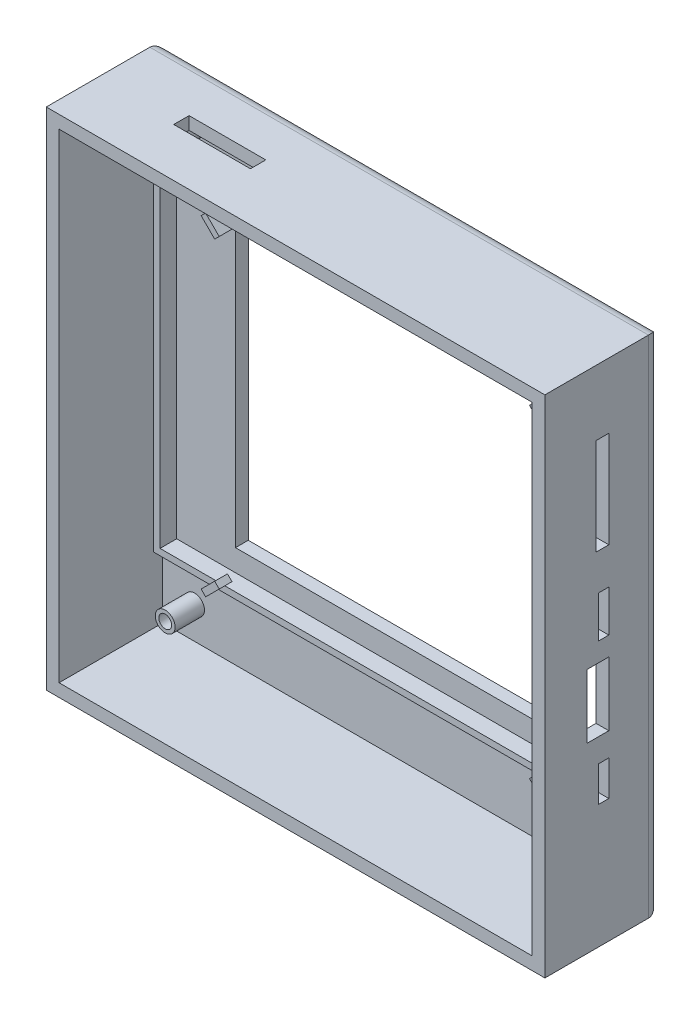
SolidWorks part; units mm, degrees
other "标注1"
sketch "草图10" plane through (-45.2426, 41.5897, 0) normal (-0.9994, 0.0059, 0.0328) x (0.0288, 0.6507, 0.7588)
ref_plane "前视基准面" through (0, 0, 0) normal (0, 0, 1) x (1, 0, 0)
ref_plane "上视基准面" through (0, 0, 0) normal (0, 1, 0) x (1, 0, 0)
ref_plane "右视基准面" through (0, 0, 0) normal (1, 0, 0) x (0, 0, -1)
sketch "外壳尺寸" plane through (0, 0, 0) normal (0, 0, 1) x (1, 0, 0)
  line L0 (-17.2361, -38.5079) -> (-14.2361, -38.5079)
  line L1 (38.764, -20.5078) -> (38.764, 15.4923)
  line L2 (-32.0459, 28.2943) -> (-38.764, 28.2943) construction
  line L3 (-32.0459, 13.1812) -> (-37.5195, 13.1812) construction
  line L4 (-33.9609, 7.4653) -> (-37.4846, 7.4653) construction
  line L5 (-33.9609, 0.9479) -> (-36.9615, 0.9479) construction
  line L6 (-34.7732, -15.6918) -> (-38.0077, -15.6918) construction
  line L7 (-34.7732, -21.1918) -> (-37.659, -21.1918) construction
  line L8 (-34.9146, -2.0109) -> (-36.6806, -2.0109) construction
  line L9 (-34.8191, -12.0127) -> (-36.3783, -12.0127) construction
  line L10 (16.4218, 37.9891) -> (16.4218, 33.2886) construction
  line L11 (28.422, 38.5079) -> (28.422, 33.6659) construction
  line L12 (-33.7426, -11.5127) -> (-35.165, -11.5127) construction
  line L13 (1.7639, 41.5897) -> (1.7639, -41.6804) construction
  line L14 (-35.165, -2.5109) -> (-33.7655, -2.5109) construction
  line L15 (45.0157, -1.0079) -> (-45.2426, -1.0079) construction
  line L16 (27.422, 35.861) -> (27.422, 36.7889) construction
  line L17 (17.4218, 35.861) -> (17.4218, 36.805) construction
  line L19 (-37.2361, -40.5079) -> (40.7639, -40.5079)
  line L20 (-37.2361, -40.5079) -> (-37.2361, 38.4921)
  line L21 (-37.2361, 38.4921) -> (40.7639, 38.4921)
  line L22 (40.7639, -40.5079) -> (40.7639, 38.4921)
  line L23 (-37.2361, -40.5079) -> (40.7639, 38.4921) construction
  line L24 (-37.2361, 38.4921) -> (40.7639, -40.5079) construction
  line L31 (-35.2362, -38.5079) -> (-17.2361, -38.5079)
  line L32 (-14.2361, -38.5079) -> (38.764, -38.5079)
  line L33 (38.764, -38.5079) -> (38.764, -20.5078)
  line L34 (38.764, 15.4923) -> (38.764, 36.4923)
  line L35 (38.764, 36.4923) -> (-35.2362, 36.4923)
  line L36 (-35.2362, 36.4923) -> (-35.2362, -38.5079)
  arc A0 (6.4148, 25.6401) -> (-2.8859, 25.6425) centre (1.7645, 25.6401) ccw construction
  arc A1 (-2.8859, 25.6377) -> (6.4148, 25.6401) centre (1.7645, 25.6401) ccw construction
  arc A2 (0.4641, 25.6357) -> (0.4641, 25.6425) centre (1.7641, 25.6391) ccw construction
  arc A3 (-2.2359, 25.6384) -> (-2.2359, 25.6425) centre (1.7643, 25.6405) ccw construction
  circle A4 centre (1.7639, 25.6423) radius 4.651 construction
  circle A5 centre (-30.1798, 31.4921) radius 1 construction
  circle A6 centre (33.764, 31.4923) radius 1 construction
  circle A7 centre (33.764, -33.5078) radius 1 construction
  circle A8 centre (-30.2361, -33.5078) radius 1 construction
  point P51 (1.7639, -1.0079)
  point P52 (1.7639, -1.0079)
  dimension "D9" = 2
  dimension "D10" = 2
  dimension "D11" = 2
  dimension "D12" = 2
  dimension "D21" = 4.6504
  dimension "D1" = 37.0001
  dimension "D2" = 37.5002
  dimension "D3" = 1
  dimension "D4" = 1
  dimension "D5" = 0.5
  dimension "D6" = 0.5
  dimension "D7" = 37.0001
  dimension "D8" = 37.5
  dimension "D13" = 5.0002
  dimension "D14" = 5.0564
  dimension "D15" = 5
  dimension "D16" = 5
  dimension "D17" = 5
  dimension "D18" = 5
  dimension "D19" = 5
  dimension "D20" = 5
  dimension "D22" = 10.8522
  dimension "D23" = 36.9995
  dimension "D24" = 78
  dimension "D25" = 79
sketch "上盖" plane through (0, 0, 0) normal (0, 0, 1) x (1, 0, 0)
  line L0 (-17.2361, -38.5079) -> (-14.2361, -38.5079)
  line L1 (38.764, -20.5078) -> (38.764, 15.4923)
  line L2 (-32.0459, 28.2943) -> (-38.764, 28.2943) construction
  line L3 (-32.0459, 13.1812) -> (-37.5195, 13.1812) construction
  line L4 (-33.9609, 7.4653) -> (-37.4846, 7.4653) construction
  line L5 (-33.9609, 0.9479) -> (-36.9615, 0.9479) construction
  line L6 (-34.7732, -15.6918) -> (-38.0077, -15.6918) construction
  line L7 (-34.7732, -21.1918) -> (-37.659, -21.1918) construction
  line L8 (-34.9146, -2.0109) -> (-36.6806, -2.0109) construction
  line L9 (-34.8191, -12.0127) -> (-36.3783, -12.0127) construction
  line L10 (16.4218, 37.9891) -> (16.4218, 33.2886) construction
  line L11 (28.422, 38.5079) -> (28.422, 33.6659) construction
  line L12 (-33.7426, -11.5127) -> (-35.165, -11.5127) construction
  line L13 (1.7639, 41.5897) -> (1.7639, -41.6804) construction
  line L14 (-35.165, -2.5109) -> (-33.7655, -2.5109) construction
  line L15 (45.0157, -1.0079) -> (-45.2426, -1.0079) construction
  line L16 (27.422, 35.861) -> (27.422, 36.7889) construction
  line L17 (17.4218, 35.861) -> (17.4218, 36.805) construction
  line L19 (-37.2361, -40.5079) -> (40.7639, -40.5079)
  line L20 (-37.2361, -40.5079) -> (-37.2361, 38.4921)
  line L21 (-37.2361, 38.4921) -> (40.7639, 38.4921)
  line L22 (40.7639, -40.5079) -> (40.7639, 38.4921)
  line L23 (-37.2361, -40.5079) -> (40.7639, 38.4921) construction
  line L24 (-37.2361, 38.4921) -> (40.7639, -40.5079) construction
  line L31 (-35.2362, -38.5079) -> (-17.2361, -38.5079)
  line L32 (-14.2361, -38.5079) -> (38.764, -38.5079)
  line L33 (38.764, -38.5079) -> (38.764, -20.5078)
  line L34 (38.764, 15.4923) -> (38.764, 36.4923)
  line L35 (38.764, 36.4923) -> (-35.2362, 36.4923)
  line L36 (-35.2362, 36.4923) -> (-35.2362, -38.5079)
  arc A0 (6.4148, 25.6401) -> (-2.8859, 25.6425) centre (1.7645, 25.6401) ccw construction
  arc A1 (-2.8859, 25.6377) -> (6.4148, 25.6401) centre (1.7645, 25.6401) ccw construction
  arc A2 (0.4641, 25.6357) -> (0.4641, 25.6425) centre (1.7641, 25.6391) ccw construction
  arc A3 (-2.2359, 25.6384) -> (-2.2359, 25.6425) centre (1.7643, 25.6405) ccw construction
  circle A4 centre (1.7639, 25.6423) radius 4.651 construction
  circle A5 centre (-30.1798, 31.4921) radius 1 construction
  circle A6 centre (33.764, 31.4923) radius 1 construction
  circle A7 centre (33.764, -33.5078) radius 1 construction
  circle A8 centre (-30.2361, -33.5078) radius 1 construction
  point P51 (1.7639, -1.0079)
  point P52 (1.7639, -1.0079)
  point P59 (16.4218, 36.4923)
  point P60 (28.422, 36.4923)
  dimension "D9" = 2
  dimension "D10" = 2
  dimension "D11" = 2
  dimension "D12" = 2
  dimension "D21" = 4.6504
  dimension "D1" = 37.0001
  dimension "D2" = 37.5002
  dimension "D3" = 1
  dimension "D4" = 1
  dimension "D5" = 0.5
  dimension "D6" = 0.5
  dimension "D7" = 37.0001
  dimension "D8" = 37.5
  dimension "D13" = 5.0002
  dimension "D14" = 5.0564
  dimension "D15" = 5
  dimension "D16" = 5
  dimension "D17" = 5
  dimension "D18" = 5
  dimension "D19" = 5
  dimension "D20" = 5
  dimension "D22" = 10.8522
  dimension "D23" = 36.9995
  dimension "D24" = 78
  dimension "D25" = 79
extrude "外壳" add sketch "上盖" against normal blind 18.2
sketch "上盖面板" plane through (0, 0, -18.2) normal (0, 0, -1) x (-1, 0, 0)
  line L0 (35.2362, 36.4923) -> (35.2362, -38.5079) construction
  line L1 (35.2362, 36.4923) -> (35.2362, -38.5079)
  line L2 (17.2361, -38.5079) -> (14.2361, -38.5079) construction
  line L3 (35.2362, -38.5079) -> (17.2361, -38.5079) construction
  line L4 (-40.7639, 38.4921) -> (-40.7639, -40.5079)
  line L5 (-40.7639, -40.5079) -> (37.2361, -40.5079)
  line L6 (37.2361, -40.5079) -> (37.2361, 38.4921)
  line L7 (37.2361, 38.4921) -> (-40.7639, 38.4921)
  line L8 (-40.7639, 38.4921) -> (-40.7639, -40.5079)
  line L9 (-40.7639, -40.5079) -> (37.2361, -40.5079)
  line L10 (37.2361, -40.5079) -> (37.2361, 38.4921)
  line L11 (37.2361, 38.4921) -> (-40.7639, 38.4921)
  line L12 (14.2361, -38.5079) -> (-38.764, -38.5079) construction
  line L13 (-38.764, -38.5079) -> (-38.764, -20.5078) construction
  line L14 (-38.764, -20.5078) -> (-38.764, 15.4923) construction
  line L15 (-38.764, 15.4923) -> (-38.764, 36.4923) construction
  line L16 (-38.764, 36.4923) -> (35.2362, 36.4923) construction
  line L17 (17.2361, -38.5079) -> (14.2361, -38.5079)
  line L18 (35.2362, -38.5079) -> (17.2361, -38.5079)
  line L19 (14.2361, -38.5079) -> (-38.764, -38.5079)
  line L20 (-38.764, -38.5079) -> (-38.764, -20.5078)
  line L21 (-38.764, -20.5078) -> (-38.764, 15.4923)
  line L22 (-38.764, 15.4923) -> (-38.764, 36.4923)
  line L23 (-38.764, 36.4923) -> (35.2362, 36.4923)
  line L24 (-36.3639, -26.0079) -> (32.8361, -26.0079)
  line L29 (-36.3639, -26.0079) -> (-36.3639, 23.9921)
  line L30 (-36.3639, 23.9921) -> (32.8361, 23.9921)
  line L35 (32.8361, -26.0079) -> (32.8361, 23.9921)
  line L36 (-36.3639, -26.0079) -> (32.8361, 23.9921) construction
  line L37 (-36.3639, 23.9921) -> (32.8361, -26.0079) construction
  line L38 (-33.7639, -22.6079) -> (23.8361, -22.6079)
  line L39 (-33.7639, -22.6079) -> (-33.7639, 20.5921)
  line L40 (-33.7639, 20.5921) -> (23.8361, 20.5921)
  line L41 (23.8361, -22.6079) -> (23.8361, 20.5921)
  line L42 (-33.7639, -22.6079) -> (23.8361, 20.5921) construction
  line L43 (-33.7639, 20.5921) -> (23.8361, -22.6079) construction
  line L44 (-45.0157, -1.0079) -> (45.2426, -1.0079) construction
  line L45 (-45.0157, -1.0079) -> (45.2426, -1.0079) construction
  line L46 (-1.7639, 41.5897) -> (-1.7639, -41.6804) construction
  line L47 (-1.7639, 41.5897) -> (-1.7639, -41.6804) construction
  point P8 (-1.7639, -1.0079)
  point P19 (-4.9639, -1.0079)
  line M11 (35.2362, 36.4923) -> (35.2362, -38.5079)
  line M12 (35.2362, -38.5079) -> (-38.764, -38.5079)
  line M13 (-38.764, -38.5079) -> (-38.764, 36.4923)
  line M14 (-38.764, 36.4923) -> (35.2362, 36.4923)
  dimension "D2" = 50
  dimension "D3" = 69.2
  dimension "D4" = 74.0001
  dimension "D5" = 75.0002
  dimension "D6" = 43.2
  dimension "D7" = 57.6
  dimension "D8" = 2.6
  dimension "D9" = 3.4
  dimension "D1" = 0
extrude "上盖面板带LCD" add sketch "上盖面板" against normal blind 2 contours L35 L24 L29 L30 M11 M14 M13 M12 | L24 L35 L30 L29 L41 L38 L39 L40 region at (-34.1825, -1.0078, -18.2) region at (35.5102, -1.0079, -18.2)
sketch "草图6" plane through (0, 0, -16.2) normal (0, 0, 1) x (1, 0, 0)
  line L4 (-35.2362, 36.4923) -> (-35.2362, -38.5079)
  line L5 (-35.2362, -38.5079) -> (38.764, -38.5079)
  line L6 (38.764, -38.5079) -> (38.764, 36.4923)
  line L7 (38.764, 36.4923) -> (-35.2362, 36.4923)
  line L8 (-35.2362, 36.4923) -> (-35.2362, -38.5079)
  line L9 (-35.2362, -38.5079) -> (38.764, -38.5079)
  line L10 (38.764, -38.5079) -> (38.764, 36.4923)
  line L11 (38.764, 36.4923) -> (-35.2362, 36.4923)
  line L27 (33.7639, -22.6079) -> (33.7639, 20.5921) construction
  line L31 (36.3639, -26.0079) -> (36.3639, 23.9921) construction
  line L32 (36.3639, -26.0079) -> (-32.8361, -26.0079) construction
  line L33 (-32.8361, -26.0079) -> (-32.8361, 23.9921) construction
  line L34 (36.3639, 23.9921) -> (-32.8361, 23.9921) construction
  line L35 (36.3639, -26.0079) -> (36.3639, 23.9921) construction
  line L36 (36.3639, -26.0079) -> (-32.8361, -26.0079)
  line L37 (-32.8361, -26.0079) -> (-32.8361, 23.9921) construction
  line L38 (36.3639, 23.9921) -> (-32.8361, 23.9921)
  line L39 (-33.0361, 23.9921) -> (-33.0361, -26.0079)
  line L40 (36.4639, -26.0079) -> (36.4639, 23.9921)
  line L41 (-33.0361, 23.9921) -> (-32.8361, 23.9921)
  line L42 (-33.0361, -26.0079) -> (-32.8361, -26.0079)
  line L43 (36.3639, -26.0079) -> (36.4639, -26.0079)
  line L44 (36.3639, 23.9921) -> (36.4639, 23.9921)
  dimension "D2" = 0.2
  dimension "D3" = 43.2
  dimension "D4" = 0.2
  dimension "D1" = 0
extrude "LCD边框" add sketch "草图6" along normal blind 2.6 thin contours L39 L42 L36 L43 L40 L44 L38 L41 thin type one direction wall 1
sketch "草图7" plane through (0, 0, -13.6) normal (0, 0, 1) x (1, 0, 0)
  line L0 (-64.1393, -14.0447) -> (-61.9924, -12.0557)
  line L1 (-61.9924, -12.0557) -> (-61.4445, -12.647)
  line L2 (-61.4445, -12.647) -> (-63.5914, -14.6361)
  line L3 (-63.5914, -14.6361) -> (-64.1393, -14.0447)
  line L4 (-59.1855, -16.6901) -> (-56.7939, -16.302)
  line L5 (-56.7939, -16.302) -> (-56.9226, -15.5087)
  line L6 (-56.9226, -15.5087) -> (-59.3142, -15.8968)
  line L7 (-59.3142, -15.8968) -> (-59.1855, -16.6901)
  line L8 (-53.3864, -16.302) -> (-50.4914, -15.5087)
  line L9 (-50.4914, -15.5087) -> (-50.7967, -14.3944)
  line L10 (-50.7967, -14.3944) -> (-53.8662, -15.2356)
  line L11 (-23.9042, -27.0079) -> (-21.7828, -24.8865)
  line L12 (-34.0361, -27.0079) -> (37.4639, -27.0079) construction
  line L13 (-21.7828, -24.8865) -> (-22.4899, -24.1794)
  line L14 (-23.9042, -27.0079) -> (-24.6113, -26.3008)
  line L15 (-24.6113, -26.3008) -> (-22.4899, -24.1794)
  line L16 (-34.0361, -27.0079) -> (37.4639, -27.0079) construction
  line L17 (27.4611, -27.0079) -> (29.5824, -24.8865)
  line L18 (29.5824, -24.8865) -> (28.8753, -24.1794)
  line L19 (27.4611, -27.0079) -> (26.754, -26.3008)
  line L20 (26.754, -26.3008) -> (28.8753, -24.1794)
  line L21 (45.0157, -1.0079) -> (-45.2426, -1.0079) construction
  line L22 (45.0157, -1.0079) -> (-45.2426, -1.0079) construction
  line L23 (26.754, 24.285) -> (28.8753, 22.1637)
  line L24 (27.4611, 24.9921) -> (26.754, 24.285)
  line L25 (29.5824, 22.8708) -> (28.8753, 22.1637)
  line L26 (27.4611, 24.9921) -> (29.5824, 22.8708)
  line L27 (-24.6113, 24.285) -> (-22.4899, 22.1637)
  line L28 (-23.9042, 24.9921) -> (-24.6113, 24.285)
  line L29 (-21.7828, 22.8708) -> (-22.4899, 22.1637)
  line L30 (-23.9042, 24.9921) -> (-21.7828, 22.8708)
  dimension "D1" = 1
  dimension "D2" = 45
  dimension "D3" = 3
  dimension "D4" = 1
  dimension "D5" = 3
  dimension "D6" = 45
extrude "LCD卡扣" add sketch "草图7" along normal blind 2 contours L30 L29 L27 L28 | L26 L25 L23 L24 | L17 L18 L20 L19 | L15 L13 L11 L14
sketch "草图9" plane through (0, 0, -16.2) normal (0, 0, 1) x (1, 0, 0)
  line L4 (-35.2362, 36.4923) -> (-35.2362, -38.5079)
  line L5 (-35.2362, -38.5079) -> (38.764, -38.5079)
  line L6 (38.764, -38.5079) -> (38.764, 36.4923)
  line L7 (38.764, 36.4923) -> (-35.2362, 36.4923)
  line L8 (-35.2362, 36.4923) -> (-35.2362, -38.5079)
  line L9 (-35.2362, -38.5079) -> (38.764, -38.5079)
  line L10 (38.764, -38.5079) -> (38.764, 36.4923)
  line L11 (38.764, 36.4923) -> (-35.2362, 36.4923)
  circle A0 centre (-30.2361, -33.5078) radius 1 construction
  circle A1 centre (33.764, -33.5078) radius 1 construction
  circle A2 centre (33.764, 31.4923) radius 1 construction
  circle A3 centre (-30.1798, 31.4921) radius 1 construction
  circle A4 centre (-30.2361, -33.5078) radius 1
  circle A5 centre (33.764, -33.5078) radius 1
  circle A6 centre (33.764, 31.4923) radius 1
  circle A7 centre (-30.1798, 31.4921) radius 1
  circle A8 centre (-30.1798, 31.4921) radius 1.55
  circle A9 centre (33.764, 31.4923) radius 1.55
  circle A10 centre (33.764, -33.5078) radius 1.55
  circle A11 centre (-30.2361, -33.5078) radius 1.55
  dimension "D2" = 3.1
  dimension "D3" = 3.1
  dimension "D4" = 3.1
  dimension "D5" = 3.1
  dimension "D6" = 2
  dimension "D7" = 2
  dimension "D8" = 2
  dimension "D9" = 2
  dimension "D1" = 0
extrude "PCB螺丝位" add sketch "草图9" along normal up to surface (4.6 mm away) contours A8 A7 | A9 A6 | A10 A5 | A11 A4 region at (-31.6859, 31.4921, -16.2) region at (32.2578, 31.4923, -16.2) region at (32.2578, -33.5078, -16.2) region at (-31.7423, -33.5078, -16.2) up to face at (-23.1971, -25.5936, -11.6)
sketch "草图11" plane through (-35.2362, 0, 0) normal (1, 0, 0) x (0, 0, -1)
  line L0 (11.6, -38.5079) -> (11.6, 36.4923)
  line L1 (10, -38.5079) -> (10, 36.4923)
  line L2 (10, 28.2923) -> (8, 28.2923)
  line L3 (8, 13.1823) -> (10, 13.1823)
  line L4 (16.2, -38.5079) -> (16.2, 36.4923)
  line L5 (16.2, 36.4923) -> (0, 36.4923)
  line L6 (0, 36.4923) -> (0, -38.5079)
  line L7 (0, -38.5079) -> (16.2, -38.5079)
  line L8 (16.2, -38.5079) -> (16.2, 36.4923)
  line L9 (16.2, 36.4923) -> (0, 36.4923)
  line L10 (0, 36.4923) -> (0, -38.5079)
  line L11 (0, -38.5079) -> (16.2, -38.5079)
  line L12 (13.6, -24.8865) -> (13.6, -24.1794)
  line L13 (13.6, -24.1794) -> (11.6, -24.1794)
  line L14 (11.6, -24.1794) -> (11.6, -24.8865)
  line L15 (11.6, -24.8865) -> (13.6, -24.8865)
  line L16 (13.6, -24.8865) -> (13.6, -24.1794)
  line L17 (13.6, -24.1794) -> (11.6, -24.1794)
  line L18 (11.6, -24.1794) -> (11.6, -24.8865)
  line L19 (11.6, -24.8865) -> (13.6, -24.8865)
  line L20 (16.2, -26.0079) -> (16.2, 23.9921)
  line L21 (16.2, 23.9921) -> (13.6, 23.9921)
  line L22 (13.6, 23.9921) -> (13.6, -26.0079)
  line L23 (13.6, -26.0079) -> (16.2, -26.0079)
  line L24 (16.2, -26.0079) -> (16.2, 23.9921)
  line L25 (16.2, 23.9921) -> (13.6, 23.9921)
  line L26 (13.6, 23.9921) -> (13.6, -26.0079)
  line L27 (13.6, -26.0079) -> (16.2, -26.0079)
  line L29 (8.4, 0.9523) -> (10, 0.9523)
  line L30 (5.93, -2.0077) -> (10, -2.0077)
  line L31 (5.93, -12.0077) -> (10, -12.0077)
  line L32 (8.4, -15.6877) -> (10, -15.6877)
  line L33 (8.4, -21.1877) -> (10, -21.1877)
  line L34 (8, 28.2923) -> (8, 13.1823)
  line L35 (8.4, 7.4623) -> (8.4, 0.9523)
  line L36 (6.6, -2.0077) -> (6.6, -12.0077)
  line L37 (8.4, -15.6877) -> (8.4, -21.1877)
  line L38 (5.93, -2.0077) -> (6.6, -2.0077)
  line L39 (5.93, -12.0077) -> (6.6, -12.0077)
  line L40 (8.4, 7.4623) -> (10, 7.4623)
  dimension "D4" = 1.6
  dimension "D5" = 8.2
  dimension "D6" = 23.31
  dimension "D7" = 29.03
  dimension "D8" = 35.54
  dimension "D9" = 57.68
  dimension "D10" = 52.18
  dimension "D11" = 48.5
  dimension "D12" = 38.5
  dimension "D13" = 2
  dimension "D14" = 1.6
  dimension "D15" = 1.6
  dimension "D16" = 3.4
  dimension "D1" = 0
  dimension "D2" = 0
  dimension "D3" = 0
extrude "切除-USB边" cut sketch "草图11" along normal up to surface (76.0001 mm away) contours L2 L34 L3 L1 | L40 L35 L29 L1 | L39 L31 L1 L30 L38 L36 | L32 L37 L33 L1 region at (-35.2362, -18.4377, -9.2) region at (-35.2362, -7.0077, -8.3) region at (-35.2362, 20.7373, -9) region at (-35.2362, 4.2073, -9.2) up to face at (40.7639, -1.0079, -9.1)
sketch "草图12" plane through (0, 36.4923, 0) normal (0, -1, 0) x (1, 0, 0)
  line L0 (-22.4899, -13.6) -> (-21.7828, -13.6) construction
  line L1 (-21.7828, -13.6) -> (-21.7828, -11.6) construction
  line L2 (-21.7828, -11.6) -> (-22.4899, -11.6) construction
  line L3 (-22.4899, -11.6) -> (-22.4899, -13.6) construction
  line L4 (-33.0361, -16.2) -> (36.4639, -16.2) construction
  line L5 (36.4639, -16.2) -> (36.4639, -13.6) construction
  line L6 (36.4639, -13.6) -> (28.4611, -13.6) construction
  line L7 (28.4611, -13.6) -> (27.0469, -13.6) construction
  line L8 (27.0469, -13.6) -> (-22.9042, -13.6) construction
  line L9 (-22.9042, -13.6) -> (-24.3184, -13.6) construction
  line L10 (-24.3184, -13.6) -> (-33.0361, -13.6) construction
  line L11 (-33.0361, -13.6) -> (-33.0361, -16.2) construction
  line L12 (-22.4899, -13.6) -> (-21.7828, -13.6)
  line L13 (-21.7828, -13.6) -> (-21.7828, -11.6)
  line L14 (-21.7828, -11.6) -> (-22.4899, -11.6)
  line L15 (-22.4899, -11.6) -> (-22.4899, -13.6)
  line L16 (-33.0361, -16.2) -> (36.4639, -16.2)
  line L17 (36.4639, -16.2) -> (36.4639, -13.6)
  line L18 (36.4639, -13.6) -> (28.4611, -13.6)
  line L19 (28.4611, -13.6) -> (27.0469, -13.6)
  line L20 (27.0469, -13.6) -> (-22.9042, -13.6)
  line L21 (-22.9042, -13.6) -> (-24.3184, -13.6)
  line L22 (-24.3184, -13.6) -> (-33.0361, -13.6)
  line L23 (-33.0361, -13.6) -> (-33.0361, -16.2)
  line L24 (-33.0361, -13.6) -> (-33.0361, 3.8074) construction
  line L25 (36.4639, -13.6) -> (36.4639, 2.3429) construction
  line L26 (-33.0361, -11.6) -> (36.4639, -11.6)
  line L27 (-33.0361, -10) -> (36.4639, -10)
  line L28 (-24.8962, -7.6) -> (-24.8962, -10)
  line L29 (-12.8962, -7.6) -> (-12.8962, -10)
  line L30 (-24.8962, -7.6) -> (-12.8962, -7.6)
  line L32 (-35.2362, -16.2) -> (38.764, -16.2)
  line L33 (38.764, -16.2) -> (38.764, 0)
  line L34 (38.764, 0) -> (-35.2362, 0)
  line L35 (-35.2362, 0) -> (-35.2362, -16.2)
  line L36 (-35.2362, -16.2) -> (38.764, -16.2)
  line L37 (38.764, -16.2) -> (38.764, 0)
  line L38 (38.764, 0) -> (-35.2362, 0)
  line L39 (-33.0361, -16.2) -> (36.4639, -16.2)
  line L40 (36.4639, -16.2) -> (36.4639, -13.6)
  line L41 (36.4639, -13.6) -> (28.4611, -13.6)
  line L42 (28.4611, -13.6) -> (27.0469, -13.6)
  line L43 (27.0469, -13.6) -> (-22.9042, -13.6)
  line L44 (-22.9042, -13.6) -> (-24.3184, -13.6)
  line L45 (-24.3184, -13.6) -> (-33.0361, -13.6)
  line L46 (-33.0361, -13.6) -> (-33.0361, -16.2)
  line L47 (-33.0361, -16.2) -> (36.4639, -16.2)
  line L48 (36.4639, -16.2) -> (36.4639, -13.6)
  line L49 (36.4639, -13.6) -> (28.4611, -13.6)
  line L50 (28.4611, -13.6) -> (27.0469, -13.6)
  line L51 (27.0469, -13.6) -> (-22.9042, -13.6)
  line L52 (-22.9042, -13.6) -> (-24.3184, -13.6)
  line L53 (-24.3184, -13.6) -> (-33.0361, -13.6)
  line L54 (-33.0361, -13.6) -> (-33.0361, -16.2)
  line L55 (-35.2362, 0) -> (-35.2362, -16.2)
  dimension "D1" = 1.6
  dimension "D2" = 0
  dimension "D3" = 10.34
  dimension "D4" = 22.34
  dimension "D6" = 2.4
  dimension "D5" = 0
extrude "切除-按钮" cut sketch "草图12" against normal up to next contours L27 region at (-18.8962, 36.4923, -8.8)
sketch "草图13" plane through (0, 36.4923, 0) normal (0, -1, 0) x (1, 0, 0)
  line L0 (38.764, 0) -> (-35.2362, 0) construction
  line L4 (-22.4899, -13.6) -> (-21.7828, -13.6)
  line L5 (-21.7828, -13.6) -> (-21.7828, -11.6)
  line L6 (-21.7828, -11.6) -> (-22.4899, -11.6)
  line L7 (-22.4899, -11.6) -> (-22.4899, -13.6)
  line L8 (-22.4899, -13.6) -> (-21.7828, -13.6)
  line L9 (-21.7828, -13.6) -> (-21.7828, -11.6)
  line L10 (-21.7828, -11.6) -> (-22.4899, -11.6)
  line L11 (-22.4899, -11.6) -> (-22.4899, -13.6)
  dimension "D2" = 11.6
  dimension "D1" = 0
sketch "草图14" plane through (0, 0, 0) normal (0, 0, 1) x (1, 0, 0)
  line L0 (40.7639, -40.5079) -> (40.7639, 38.4921) construction
  line L1 (-37.2361, -40.5079) -> (40.7639, -40.5079) construction
  line L2 (-37.2361, -40.5079) -> (-37.2361, 38.4921) construction
  line L3 (-37.2361, 38.4921) -> (40.7639, 38.4921) construction
  line L4 (40.7639, -40.5079) -> (40.7639, 38.4921)
  line L5 (-37.2361, -40.5079) -> (40.7639, -40.5079)
  line L6 (-37.2361, -40.5079) -> (-37.2361, 38.4921)
  line L7 (-37.2361, 38.4921) -> (40.7639, 38.4921)
  circle A0 centre (33.764, -33.5078) radius 1.55 construction
  circle A1 centre (33.764, -33.5078) radius 1 construction
  circle A2 centre (-30.2361, -33.5078) radius 1.55 construction
  circle A3 centre (-30.2361, -33.5078) radius 1 construction
  circle A4 centre (-30.1798, 31.4921) radius 1.55 construction
  circle A5 centre (-30.1798, 31.4921) radius 1 construction
  circle A6 centre (33.764, 31.4923) radius 1.55 construction
  circle A7 centre (33.764, 31.4923) radius 1 construction
  arc A8 (-2.8859, 25.6377) -> (6.4148, 25.6401) centre (1.7645, 25.6401) ccw construction
  arc A9 (6.4148, 25.6401) -> (-2.8859, 25.6425) centre (1.7645, 25.6401) ccw construction
  circle A10 centre (33.764, -33.5078) radius 1.55
  circle A11 centre (33.764, -33.5078) radius 1
  circle A12 centre (-30.2361, -33.5078) radius 1.55
  circle A13 centre (-30.2361, -33.5078) radius 1
  circle A14 centre (-30.1798, 31.4921) radius 1.55
  circle A15 centre (-30.1798, 31.4921) radius 1
  circle A16 centre (33.764, 31.4923) radius 1.55
  circle A17 centre (33.764, 31.4923) radius 1
  arc A18 (-2.8859, 25.6377) -> (6.4148, 25.6401) centre (1.7645, 25.6401) ccw
  arc A19 (6.4148, 25.6401) -> (-2.8859, 25.6425) centre (1.7645, 25.6401) ccw
fillet "圆角1" radius 2 4 edges at (-37.2361, -1.0079, -18.2) (1.7639, -40.5079, -18.2) (40.7639, -1.0079, -18.2) (1.7639, 38.4921, -18.2)
